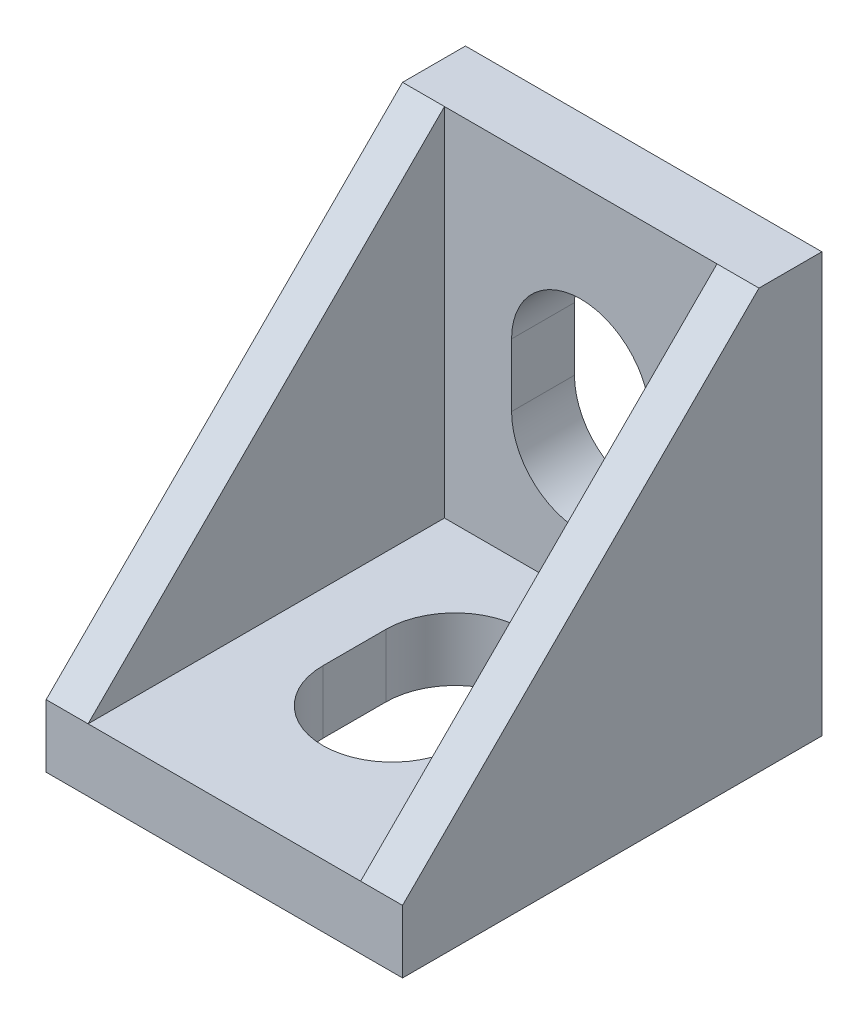
SolidWorks part; units mm, degrees
note: '?' marks a value the reader was unsure of.
ref_plane "Front Plane" through (0, 0, 0) normal (0, 0, 1) x (1, 0, 0)
ref_plane "Top Plane" through (0, 0, 0) normal (0, 1, 0) x (1, 0, 0)
ref_plane "Right Plane" through (0, 0, 0) normal (1, 0, 0) x (0, 0, -1)
ref_axis "Axis_X" through (-88.99, 0, 0) along (1, 0, 0)?
ref_axis "Axis_Y" through (0, 55, 0) along (0, -1, 0)?
ref_axis "Axis_Z" through (0, 0, -88.99) along (0, 0, 1)?
sketch "Sketch1" plane through (0, 0, 0) normal (1, 0, 0) x (0, 0, -1)
  line L1 (0, 0) -> (-20, 0)
  line L2 (0, 0) -> (0, 20)
  line L3 (0, 20) -> (-20, 20)
  line L4 (-20, 0) -> (-20, 20)
  dimension "H" = 20
extrude "Boss-Extrude1" add sketch "Sketch1" along normal mid plane 17
sketch "Sketch2" plane through (-8.5, 0, 0) normal (-1, 0, 0) x (0, 0, 1)
  line L0 (20, 20) -> (3, 20)
  line L1 (0, 20) -> (20, 20) construction
  line L2 (3, 20) -> (20, 3)
  line L3 (20, 20) -> (20, 0) construction
  line L4 (20, 3) -> (20, 20)
  line L5 (0, 0) -> (0, 20) construction
  dimension "W1" = 3
extrude "Cut-Extrude1" cut sketch "Sketch2" against normal through all
sketch "Sketch3" plane through (0, 20, 0) normal (0, 1, 0) x (1, 0, 0)
  line L0 (8.5, -20) -> (-8.5, -20) construction
  line L1 (-6.5, -20) -> (6.5, -20)
  line L2 (-6.5, -20) -> (-6.5, -3)
  line L3 (-6.5, -3) -> (6.5, -3)
  line L4 (6.5, -20) -> (6.5, -3)
  line L5 (0, 0) -> (0, -3) construction
  line L6 (8.5, 0) -> (-8.5, 0) construction
  line L7 (-8.5, 0) -> (-8.5, -3) construction
  dimension "T" = 3
  dimension "T1" = 2
extrude "Cut-Extrude2" cut sketch "Sketch3" against normal offset from surface (17 mm away) 3 up to face at (0, 0, 10)
sketch "Sketch4" plane through (-8.5, 0, 0) normal (-1, 0, 0) x (0, 0, 1)
  line L0 (4.5, 20) -> (4.5, 13.6)
  line L1 (4.5, 13.6) -> (13.6, 3)
  line L2 (13.6, 3) -> (20, 3)
  line L3 (0, 0) -> (0, 20) construction
  line L4 (0, 20) -> (3, 20) construction
  line L5 (20, 3) -> (20, 0) construction
  line L6 (4.5, 20) -> (20, 3)
  dimension "W1" = 4.5
  dimension "FIX_1" = 6.4
extrude "Cut-Extrude3" [suppressed] cut sketch "Sketch4" against normal through all
fillet "Fillet1" [suppressed] radius 2
sketch "Sketch5" plane through (0, 0, 3) normal (0, 0, 1) x (1, 0, 0)
  line L0 (0, 9) -> (0, 12) construction
  line L1 (-3.3, 9) -> (-3.3, 12)
  line L2 (3.3, 9) -> (3.3, 12)
  line L3 (8.5, 0) -> (-8.5, 0) construction
  arc A0 (-3.3, 9) -> (3.3, 9) centre (0, 9) ccw
  arc A1 (3.3, 12) -> (-3.3, 12) centre (0, 12) ccw
  point P2 (0, 10.5)
  dimension "R" = 3.3
  dimension "B" = 3
  dimension "A" = 9
extrude "Cut-Extrude4" cut sketch "Sketch5" against normal through all
sketch "Sketch6" plane through (0, 3, 0) normal (0, 1, 0) x (1, 0, 0)
  line L0 (0, -9) -> (0, -12) construction
  line L1 (3.3, -9) -> (3.3, -12)
  line L2 (-3.3, -9) -> (-3.3, -12)
  line L3 (8.5, 0) -> (-8.5, 0) construction
  arc A0 (3.3, -9) -> (-3.3, -9) centre (0, -9) ccw
  arc A1 (-3.3, -12) -> (3.3, -12) centre (0, -12) ccw
  point P2 (0, -10.5)
  dimension "R" = 3.3
  dimension "B" = 3
  dimension "A" = 9
extrude "Cut-Extrude5" cut sketch "Sketch6" against normal through all
sketch "Sketch7" plane through (0, 0, 0) normal (0, 0, -1) x (-1, 0, 0)
  line L0 (0, 20) -> (0, 0) construction
  line L1 (-2.25, 18.6) -> (2.25, 18.6)
  line L2 (-2.25, 18.6) -> (-2.25, 17)
  line L3 (-2.25, 17) -> (2.25, 17)
  line L4 (2.25, 18.6) -> (2.25, 17)
  line L5 (-2.25, 3) -> (2.25, 3)
  line L6 (-2.25, 3) -> (-2.25, 1.4)
  line L7 (-2.25, 1.4) -> (2.25, 1.4)
  line L8 (2.25, 3) -> (2.25, 1.4)
  line L9 (-8.5, 20) -> (8.5, 20) construction
  line L10 (-8.5, 0) -> (8.5, 0) construction
  dimension "W" = 4.5
  dimension "MSM_1" = 1.6
extrude "Boss-Extrude2" add sketch "Sketch7" along normal blind 1
sketch "Sketch8" plane through (0, 0, 0) normal (0, -1, 0) x (1, 0, 0)
  line L0 (0, 0) -> (0, 20) construction
  line L1 (-2.25, 18.6) -> (2.25, 18.6)
  line L2 (-2.25, 18.6) -> (-2.25, 17)
  line L3 (-2.25, 17) -> (2.25, 17)
  line L4 (2.25, 18.6) -> (2.25, 17)
  line L5 (-2.25, 3) -> (2.25, 3)
  line L6 (-2.25, 3) -> (-2.25, 1.4)
  line L7 (-2.25, 1.4) -> (2.25, 1.4)
  line L8 (2.25, 3) -> (2.25, 1.4)
  line L9 (8.5, 20) -> (-8.5, 20) construction
  line L10 (8.5, 0) -> (-8.5, 0) construction
  dimension "W" = 4.5
  dimension "MSM_1" = 1.6
extrude "Boss-Extrude3" add sketch "Sketch8" along normal blind 1
hole_wizard "Tap1" [suppressed] positions "Sketch11" profile "Sketch10" hole size "M5x0.8" standard "JIS"
sketch "Sketch11" plane through (-9.8, 0, 0) normal (-1, 0, 0) x (0, 0, 1)
  line L0 (27.6, 0) -> (0, 0) construction
  line L1 (0, 0) -> (0, 27.6) construction
  point P0 (8, 8)
  dimension "KSS_1" = 8
  dimension "KSS_2" = 8
sketch "Sketch10" plane through (-9.8, 8, 8) normal (0, 1, 0) x (0, 0, 1)
  line L0 (0, 0) -> (0, 19.6)
  line L1 (0, 19.6) -> (2.067, 19.6)
  line L2 (2.067, 19.6) -> (2.067, 0)
  line L5 (2.067, 0) -> (0, 0)
  line L11 (0, -6.35) -> (0, 107.95) construction
  dimension "FIX_5" = 4.134
  dimension "Thru Hole Depth" = 19.6
cosmetic thread "Thread1" [suppressed] parameters "FIX_4"=5
equation "\"Factor\"= 1.082532"
equation "\"KSS_1@Sketch11\" = if ( \"L@Boss-Extrude1\" < 20 , 8 , 12 )"
equation "\"KSS_2@Sketch11\"= if ( \"L@Boss-Extrude1\" < 20 , 8 , 12 )"
